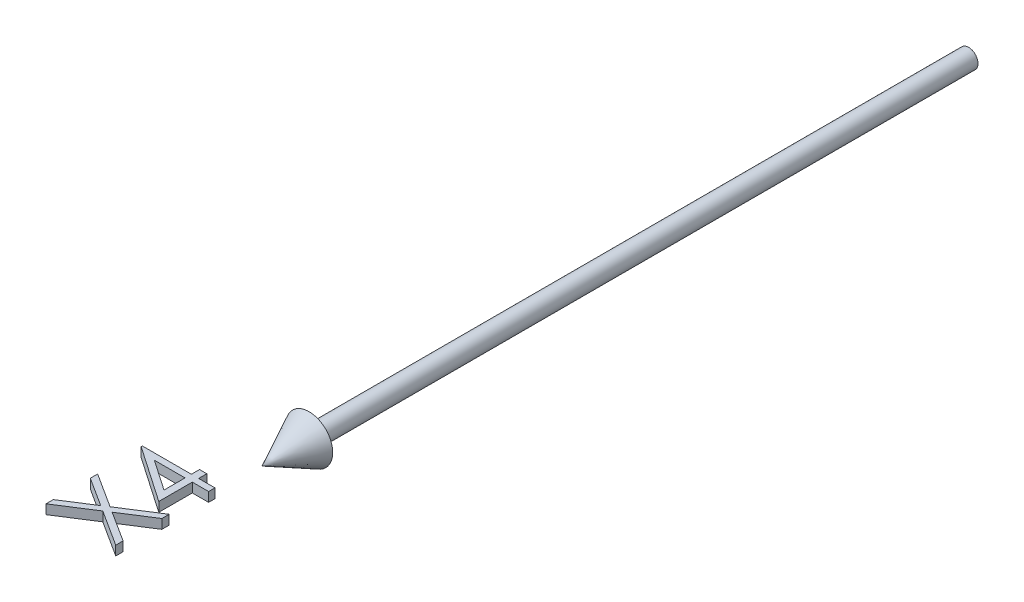
SolidWorks part; units mm, degrees
ref_plane "Front Plane" through (0, 0, 0) normal (0, 0, 1) x (1, 0, 0)
ref_plane "Top Plane" through (0, 0, 0) normal (0, 1, 0) x (1, 0, 0)
ref_plane "Right Plane" through (0, 0, 0) normal (1, 0, 0) x (0, 0, -1)
sketch "Sketch2" plane through (0, 0, 0) normal (0, 1, 0) x (1, 0, 0)
  line L0 (0, 41.95) -> (0, -114.4521) construction
  line L1 (-36.8894, 0) -> (41.4965, 0) construction
  line L2 (0, -150) -> (5, -140)
  line L3 (5, -140) -> (2, -140)
  line L4 (2, -140) -> (2, 0)
  line L5 (2, 0) -> (0, 0)
  line L6 (0, 0) -> (0, -150)
  dimension "D1" = 150
  dimension "D2" = 2
  dimension "D3" = 10
  dimension "D4" = 5
revolve "Revolve1" add sketch "Sketch2" angle 360 about L0
sketch "Sketch3" plane through (0, 0, 0) normal (0, 1, 0) x (1, 0, 0)
  line L0 (0, -157.5) -> (0, -248.2119) construction
  line L1 (-44.4332, 0) -> (53.8455, 0) construction
  text T0 "X4\r\n" font "Century Gothic" height 15
  dimension "D1" = 157.5
extrude "Boss-Extrude1" add sketch "Sketch3" against normal blind 1 and the other way blind 1 separate body
equation "\"D1@Sketch2\"=\"frame_arrow_length\""
equation "\"D2@Sketch2\"=\"frame_arrow_odA\"/2"
equation "\"D4@Sketch2\"=\"frame_arrow_head_od\""
equation "\"D3@Sketch2\"=\"frame_arrow_head_length\""
equation "\"frame_arrow_length\"=150"
equation "\"frame_arrow_head_length\"=10"
equation "\"frame_arrow_head_od\"=5"
equation "\"frame_arrow_odA\"=4"
equation "\"D1@Sketch3\"=\"frame_arrow_length\"*1.05"
